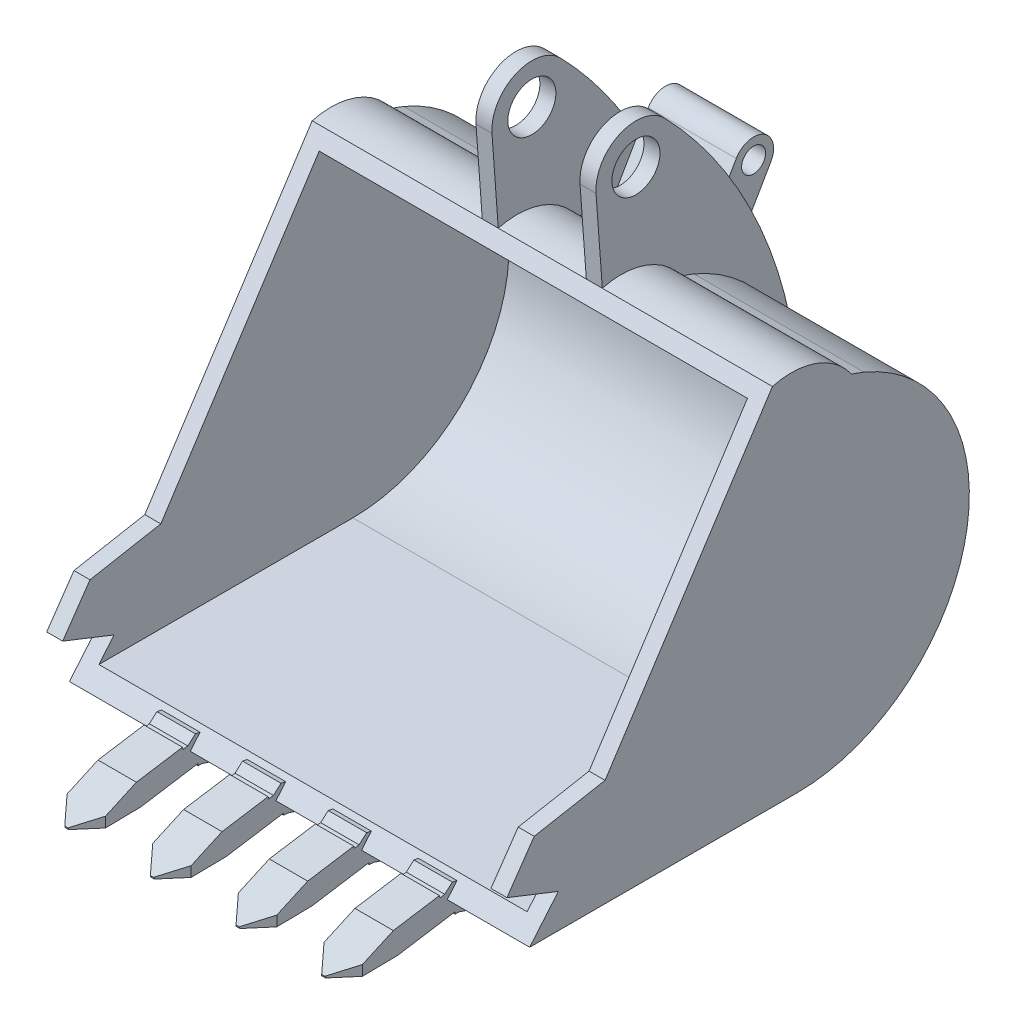
SolidWorks part; units mm, degrees
material "Stainless Steel (ferritic)"
ref_plane "Plano frontal" through (0, 0, 0) normal (0, 0, 1) x (1, 0, 0)
ref_plane "Plano superior" through (0, 0, 0) normal (0, 1, 0) x (1, 0, 0)
ref_plane "Plano direito" through (0, 0, 0) normal (1, 0, 0) x (0, 0, -1)
sketch "Sketch1" plane through (0, 0, 0) normal (1, 0, 0) x (0, 0, -1)
  line L0 (-24.8954, 174.8294) -> (543.7713, 174.8294) construction
  line L2 (-17.1313, -20.3471) -> (18.6779, 22.1841)
  line L3 (18.6779, 22.1841) -> (-45.5104, 47.4993)
  line L4 (-45.5104, 47.4993) -> (-11.4521, 96.8961)
  line L5 (-11.4521, 96.8961) -> (77.0652, 113.1649)
  line L6 (77.0652, 113.1649) -> (286.141, 434.7469)
  line L8 (286.141, 434.7469) -> (400.4899, 393.1273)
  line L9 (-17.1313, -20.3471) -> (317, -20.3471)
  arc A1 (400.4899, 393.1273) -> (317, -20.3471) centre (316.9974, 194.8199) cw
  dimension "D2" = 135
  dimension "D7" = 60
  dimension "D8" = 90
  dimension "D10" = 69
extrude "Boss-Extrude2" add sketch "Sketch1" along normal mid plane 575 contours L6 L8 A1 L9 L2 L3 L4 L5
shell "Shell1" thickness 20 removed face at (0, 0.9185, -0.7733) removed face at (0, 34.8417, 13.4162) removed face at (0, 72.1977, 28.4813) removed face at (0, 105.0305, -32.8066) removed face at (0, 273.9559, -181.6031)
sketch "Sketch4" plane through (0, 0, 0) normal (1, 0, 0) x (0, 0, -1)
  line L0 (473.4904, 471.5) -> (422.1354, 382.5506)
  line L1 (516.7916, 446.5) -> (462.8269, 353.0304)
  line L2 (286.141, 434.7469) -> (400.4899, 393.1273) construction
  line L3 (516.7916, 446.5) -> (465.4367, 357.5506) construction
  arc A0 (516.7916, 446.5) -> (473.4904, 471.5) centre (495.141, 459) ccw
  circle A1 centre (495.141, 459) radius 15
  arc A2 (317, -20.3471) -> (400.4899, 393.1273) centre (316.9974, 194.8199) ccw construction
  arc A3 (462.8269, 353.0304) -> (422.1354, 382.5506) centre (316.9974, 194.8199) ccw
  dimension "D2" = 50
  dimension "D3" = 30
  dimension "D1" = 209
  dimension "D4" = 459
  dimension "D5" = 100
  dimension "D6" = 50
extrude "Boss-Extrude3" add sketch "Sketch4" along normal mid plane 110
sketch "Sketch5" plane through (0, 0, 0) normal (1, 0, 0) x (0, 0, -1)
  line L0 (286.141, 434.7469) -> (400.4899, 393.1273) construction
  line L1 (286.141, 434.7469) -> (384.9214, 398.7938)
  arc A0 (286.141, 434.7469) -> (384.9214, 398.7938) centre (309.706, 345.8161) cw
  dimension "D1" = 92
extrude "Boss-Extrude4" add sketch "Sketch5" along normal mid plane 575
sketch "Sketch6" plane through (0, 0, 0) normal (1, 0, 0) x (0, 0, -1)
  line L0 (278.2766, 541.3203) -> (286.141, 434.7469)
  line L3 (384.9214, 398.7938) -> (400.4899, 393.1273) construction
  line L4 (384.9214, 398.7938) -> (400.4899, 393.1273)
  circle A0 centre (328.141, 545) radius 30
  arc A1 (364.0278, 579.8157) -> (278.2766, 541.3203) centre (328.141, 545) ccw
  circle A2 centre (495.141, 459) radius 15 construction
  arc A3 (364.0278, 579.8157) -> (532.0359, 202.2544) centre (-66.614, 162.0268) cw
  arc A5 (317, -20.3471) -> (400.4899, 393.1273) centre (316.9974, 194.8199) ccw construction
  arc A6 (384.9214, 398.7938) -> (286.141, 434.7469) centre (309.706, 345.8161) ccw construction
  arc A7 (532.0359, 202.2544) -> (400.4899, 393.1273) centre (316.9974, 194.8199) ccw
  arc A8 (384.9214, 398.7938) -> (286.141, 434.7469) centre (309.706, 345.8161) ccw
  dimension "D1" = 60
  dimension "D2" = 100
  dimension "D6" = 600
  dimension "D3" = 42
  dimension "D4" = 86
extrude "Boss-Extrude5" add sketch "Sketch6" along normal blind 20 from offset 55 contours A8 L4 A7 A3 A1 L0 A0 region at (0, 460.2715, -387.2474)
mirror "Mirror1" about plane through (0, 0, 0) normal (1, 0, 0) of "Boss-Extrude5"
ref_plane "Plane1" through (-184.5, 0, 0) normal (1, 0, 0) x (0, 0, -1)
sketch "Sketch9" plane through (-184.5, 0, 0) normal (1, 0, 0) x (0, 0, -1)
  line L0 (-317.6993, 30.9554) -> (592.9673, 30.9554) construction
  line L1 (-2.208, -40.939) -> (-7.305, -40.939)
  line L3 (-10.7657, -4.5785) -> (-4.894, -5.8127)
  line L4 (-17.1313, -20.3471) -> (18.6779, 22.1841) construction
  line L5 (-10.7657, -4.5785) -> (-20.2571, -12.9388)
  line L6 (-7.305, -40.939) -> (-7.7449, -38.4006)
  line L7 (-20.2571, -12.9388) -> (-26.1837, -13.8743)
  line L8 (-26.1837, -13.8743) -> (-26.8717, -11.0482)
  line L9 (-26.8717, -11.0482) -> (-84.4409, -20.1349)
  line L10 (-84.4409, -20.1349) -> (-147.9411, -48.7779)
  line L11 (-147.9411, -48.7779) -> (-147.4681, -50.7212)
  line L12 (-147.4681, -50.7212) -> (-78.8645, -49.6261)
  line L13 (-78.8645, -49.6261) -> (-7.7449, -38.4006)
  line L14 (-52.5583, -15.1026) -> (-47.881, -44.7357) construction
  line L15 (-50.2197, -29.9191) -> (-147.7046, -49.7495) construction
  line L16 (-2.208, -40.939) -> (5.3278, -43.5576)
  line L17 (5.3278, -43.5576) -> (63.6014, -34.3279)
  line L18 (63.6014, -34.3279) -> (62.8687, -20.3471)
  line L19 (-17.1313, -20.3471) -> (317, -20.3471) construction
  line L20 (-4.894, -5.8127) -> (-17.1313, -20.3471)
  line L21 (62.8687, -20.3471) -> (-17.1313, -20.3471)
  dimension "D1" = 19
  dimension "D2" = 6
  dimension "D4" = 59
  dimension "D6" = 9
  dimension "D7" = 80
  dimension "D8" = 12
  dimension "D9" = 72
  dimension "D3" = 14
  dimension "D10" = 30
  dimension "D5" = 96
  dimension "D12" = 2
  dimension "D13" = 6
  dimension "D14" = 68.6036
extrude "Boss-Extrude6" add sketch "Sketch9" along normal blind 48 contours L9 L10 L11 L12 L13 L6 L1 L16 L17 L18 L21 L20 L3 L5 L7 L8
sketch "Sketch10" plane through (0, 0, 0) normal (0, 1, 0) x (1, 0, 0)
  line L0 (-184.5, -123.0746) -> (-162.5, -147.9411)
  line L1 (-184.5, -84.4409) -> (-184.5, -147.9411) construction
  line L2 (-136.5, -147.9411) -> (-184.5, -147.9411) construction
  line L4 (-158.5, -147.9411) -> (-136.5, -123.0746)
  line L5 (-136.5, -84.4409) -> (-136.5, -147.9411) construction
  line L6 (-160.5, -147.9411) -> (-160.5, -101.1996) construction
  line L7 (-184.5, -123.0746) -> (-184.5, -147.9411)
  line L8 (-162.5, -147.9411) -> (-184.5, -147.9411)
  line L9 (-158.5, -147.9411) -> (-136.5, -147.9411)
  line L10 (-136.5, -147.9411) -> (-136.5, -123.0746)
  dimension "D1" = 83
  dimension "D2" = 4
extrude "Cut-Extrude1" cut sketch "Sketch10" against normal through all both and the other way through all
pattern_linear "LPattern1" count 4 spacing 107 along (1, 0, 0) of "Boss-Extrude6", "Cut-Extrude1"
